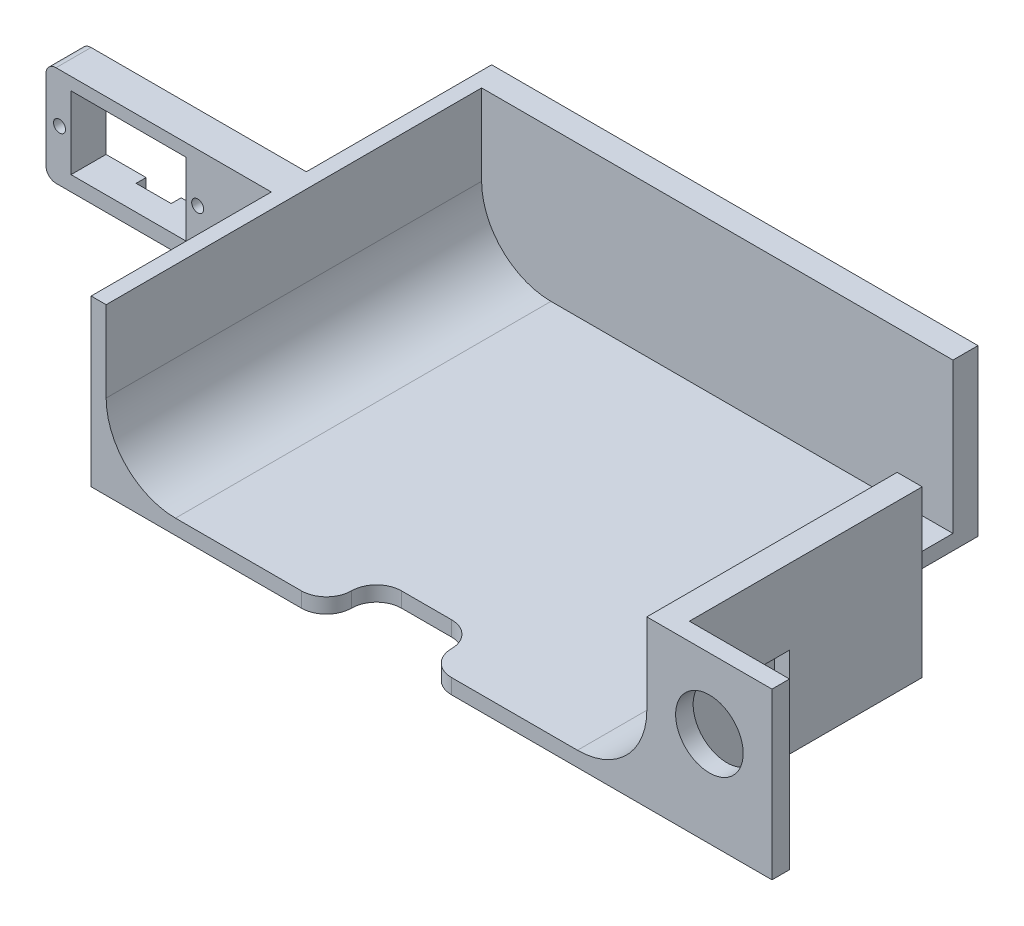
SolidWorks part; units mm, degrees
ref_plane "Plan de face" through (0, 0, 0) normal (0, 0, 1) x (1, 0, 0)
ref_plane "Plan de dessus" through (0, 0, 0) normal (0, 1, 0) x (1, 0, 0)
ref_plane "Plan de droite" through (0, 0, 0) normal (1, 0, 0) x (0, 0, -1)
sketch "Esquisse1" plane through (0, 0, 0) normal (0, 1, 0) x (1, 0, 0)
  line L1 (0, 0) -> (138, 0)
  line L2 (0, 0) -> (0, 75)
  line L3 (0, 75) -> (138, 75)
  line L4 (138, 0) -> (138, 75)
  dimension "D1" = 138
  dimension "D2" = 75
extrude "Boss.-Extru.1" add sketch "Esquisse1" along normal blind 3
sketch "Esquisse2" plane through (0, 3, 0) normal (0, 1, 0) x (1, 0, 0)
  line L0 (0, 0) -> (138, 0) construction
  line L1 (0, 75) -> (5, 75)
  line L2 (0, 75) -> (0, 0)
  line L3 (0, 0) -> (5, 0)
  line L4 (5, 75) -> (5, 0)
  line L6 (138, 75) -> (113, 75)
  line L7 (138, 75) -> (138, 0)
  line L8 (138, 0) -> (113, 0)
  line L9 (113, 75) -> (113, 0)
  dimension "D1" = 25
  dimension "D2" = 5
extrude "Boss.-Extru.2" add sketch "Esquisse2" along normal blind 30
fillet "Congé1" radius 13.85 2 edges at (113, 3, -37.5) (5, 3, -37.5)
sketch "Esquisse3" plane through (0, 0, -75) normal (0, 0, -1) x (-1, 0, 0)
  line L1 (-138, 0) -> (0, 0)
  line L2 (-138, 0) -> (-138, 33)
  line L3 (-138, 33) -> (0, 33)
  line L4 (0, 0) -> (0, 33)
extrude "Boss.-Extru.3" add sketch "Esquisse3" along normal blind 5
sketch "Esquisse4" plane through (0, 0, 0) normal (-1, 0, 0) x (0, 0, 1)
  line L1 (0, 33) -> (-25, 33)
  line L2 (0, 33) -> (0, 13)
  line L3 (0, 13) -> (-25, 13)
  line L4 (-25, 33) -> (-25, 13)
  dimension "D1" = 25
  dimension "D2" = 20
extrude "Enlèv. mat.-Extru.1" [suppressed] cut sketch "Esquisse4" against normal blind 6
sketch "Esquisse5" plane through (0, 33, 0) normal (0, 1, 0) x (1, 0, 0)
  line L0 (113, 75) -> (113, 0) construction
  line L1 (138, 80) -> (118, 80)
  line L2 (138, 80) -> (138, 3.5)
  line L3 (138, 3.5) -> (118, 3.5)
  line L4 (118, 80) -> (118, 3.5)
  line L5 (113, 0) -> (138, 0) construction
  dimension "D1" = 5
  dimension "D2" = 3.5
extrude "Enlèv. mat.-Extru.2" cut sketch "Esquisse5" against normal blind 30
sketch "Esquisse6" plane through (0, 0, 0) normal (0, 0, 1) x (1, 0, 0)
  line L0 (113, 33) -> (138, 33) construction
  line L3 (138, 33) -> (138, 0) construction
  circle A0 centre (125.5, 19) radius 6.25
  dimension "D3" = 12.5
  dimension "D1" = 14
  dimension "D2" = 12.5
extrude "Enlèv. mat.-Extru.3" cut sketch "Esquisse6" against normal up to surface (3.5 mm away) up to face at (128, 18, -3.5)
sketch "Esquisse7" plane through (0, 0, -80) normal (0, 0, -1) x (-1, 0, 0)
  line L1 (-138, 0) -> (-118, 0)
  line L2 (-138, 0) -> (-138, 3)
  line L3 (-138, 3) -> (-118, 3)
  line L4 (-118, 0) -> (-118, 3)
extrude "Enlèv. mat.-Extru.4" cut sketch "Esquisse7" against normal blind 30
sketch "Esquisse8" plane through (0, 33, 0) normal (0, 1, 0) x (1, 0, 0)
  line L0 (99.15, 0) -> (99.15, 75) construction
  line L1 (118, 80) -> (99.15, 80)
  line L2 (118, 80) -> (118, 50)
  line L3 (118, 50) -> (99.15, 50)
  line L4 (99.15, 80) -> (99.15, 50)
  dimension "D1" = 30
extrude "Enlèv. mat.-Extru.5" cut sketch "Esquisse8" against normal up to surface (33 mm away) up to face at (85.3333, 0, -43.3333)
sketch "Esquisse10" plane through (118, 0, 0) normal (1, 0, 0) x (0, 0, -1)
  line L0 (50, 3) -> (3.5, 3) construction
  line L1 (15.5, 3) -> (23.5, 3)
  line L2 (15.5, 3) -> (15.5, 18)
  line L3 (15.5, 18) -> (23.5, 18)
  line L4 (23.5, 3) -> (23.5, 18)
  dimension "D1" = 12
  dimension "D2" = 8
  dimension "D3" = 15
extrude "Enlèv. mat.-Extru.6" cut sketch "Esquisse10" against normal offset from surface (3 mm away) 2 up to face at (113, 24.925, -25)
sketch "Esquisse11" plane through (0, 3, 0) normal (0, 1, 0) x (1, 0, 0)
  line L1 (115, 23.5) -> (118, 23.5)
  line L2 (115, 23.5) -> (115, 15.5)
  line L3 (115, 15.5) -> (131, 15.5)
  line L8 (138, 3.5) -> (131, 3.5)
  line L9 (131, 15.5) -> (131, 3.5)
  line L10 (138, 50) -> (138, 3.5)
  line L11 (118, 50) -> (138, 50)
  line L12 (118, 50) -> (118, 23.5)
  dimension "D1" = 12
  dimension "D2" = 7
  dimension "D3" = 20
extrude "Enlèv. mat.-Extru.7" cut sketch "Esquisse11" against normal up to surface (3 mm away) up to face at (79.05, 0, -43.3333)
sketch "Esquisse12" plane through (0, 0, 0) normal (-1, 0, 0) x (0, 0, 1)
  line L1 (-80, 33) -> (0, 33)
  line L2 (-80, 33) -> (-80, 0)
  line L3 (-80, 0) -> (0, 0)
  line L4 (0, 33) -> (0, 0)
extrude "Enlèv. mat.-Extru.8" cut sketch "Esquisse12" against normal blind 2
sketch "Esquisse13" plane through (0, 0, 0) normal (0, 0, 1) x (1, 0, 0)
  line L0 (37, 0) -> (44.5969, -20)
  line L1 (2, 0) -> (138, 0) construction
  line L2 (44.5969, -20) -> (71.5969, -20)
  line L3 (71.5969, -20) -> (78, 0)
  line L4 (78, 0) -> (37, 0)
  line L7 (113, 33) -> (113, 16.85) construction
  dimension "D1" = 35
  dimension "D2" = 27
  dimension "D3" = 35
  dimension "D4" = 20
  dimension "D5" = 21
extrude "Boss.-Extru.4" [suppressed] add sketch "Esquisse13" against normal blind 7
sketch "Esquisse14" [suppressed] plane through (0, 0, 0) normal (0, 0, 1) x (1, 0, 0)
  line L0 (44.5969, -20) -> (71.5969, -20) construction
  line L1 (46.5, -2.5) -> (69.5, -2.5)
  line L2 (46.5, -2.5) -> (46.5, -17)
  line L3 (46.5, -17) -> (69.5, -17)
  line L4 (69.5, -2.5) -> (69.5, -17)
  dimension "D1" = 23
  dimension "D2" = 9.5
  dimension "D3" = 3
  dimension "D4" = 14.5
extrude "Enlèv. mat.-Extru.9" [suppressed] cut sketch "Esquisse14" against normal up to surface (7 mm away) up to face at (131.75, 19, 0)
fillet "Congé2" [suppressed] radius 10
sketch "Esquisse15" plane through (2, 0, 0) normal (-1, 0, 0) x (0, 0, 1)
  line L0 (0, 33) -> (-80, 33) construction
  line L1 (-42.9875, 33) -> (-35.9875, 33)
  line L2 (-42.9875, 33) -> (-42.9875, 13)
  line L3 (-42.9875, 13) -> (-35.9875, 13)
  line L4 (-35.9875, 33) -> (-35.9875, 13)
  dimension "D1" = 20
  dimension "D2" = 7
extrude "Boss.-Extru.5" add sketch "Esquisse15" along normal blind 45
sketch "Esquisse16" plane through (0, 0, -35.9875) normal (0, 0, 1) x (1, 0, 0)
  line L0 (-20.5, 33) -> (-20.5, 13) construction
  line L1 (-43, 33) -> (2, 33) construction
  line L2 (-43, 13) -> (2, 13) construction
  line L3 (-43, 23) -> (2, 23) construction
  line L4 (-43, 13) -> (-43, 33) construction
  line L5 (2, 13) -> (2, 33) construction
  line L7 (-38, 30.5) -> (-15, 30.5)
  line L8 (-38, 30.5) -> (-38, 16)
  line L9 (-38, 16) -> (-15, 16)
  line L10 (-15, 30.5) -> (-15, 16)
  dimension "D1" = 23
  dimension "D2" = 14.5
  dimension "D3" = 2.5
  dimension "D4" = 5
extrude "Enlèv. mat.-Extru.10" cut sketch "Esquisse16" against normal up to surface (7 mm away) up to face at (-20.5, 23, -42.9875)
fillet "Congé3" radius 20 1 edges at (2, 13, -39.4875)
fillet "Congé4" radius 2 2 edges at (-43, 33, -39.4875) (-43, 13, -39.4875)
sketch "Esquisse18" plane through (0, 0, -42.9875) normal (0, 0, -1) x (-1, 0, 0)
  line L0 (15, 16) -> (38, 16) construction
  line L1 (23, 16) -> (30, 16)
  line L2 (23, 16) -> (23, 13)
  line L3 (23, 13) -> (30, 13)
  line L4 (30, 16) -> (30, 13)
  line L6 (41, 13) -> (16.735, 13) construction
  dimension "D1" = 8
  dimension "D2" = 8
extrude "Enlèv. mat.-Extru.11" cut sketch "Esquisse18" against normal blind 2
sketch "Esquisse20" plane through (0, 0, -42.9875) normal (0, 0, -1) x (-1, 0, 0)
  line L0 (38, 30.5) -> (15, 30.5) construction
  line L1 (10.4, 25.9) -> (15, 25.9)
  line L2 (10.4, 25.9) -> (10.4, 20.6)
  line L3 (10.4, 20.6) -> (15, 20.6)
  line L4 (15, 25.9) -> (15, 20.6)
  line L5 (38, 25.9) -> (42.6, 25.9)
  line L6 (38, 25.9) -> (38, 20.6)
  line L7 (38, 20.6) -> (42.6, 20.6)
  line L8 (42.6, 25.9) -> (42.6, 20.6)
  line L9 (15, 16) -> (23, 16) construction
  line L10 (15, 30.5) -> (15, 16) construction
  line L11 (38, 16) -> (38, 30.5) construction
  line L12 (30, 16) -> (38, 16) construction
  dimension "D1" = 4.6
  dimension "D2" = 4.6
  dimension "D3" = 4.6
  dimension "D4" = 4.6
  dimension "D5" = 4.6
  dimension "D6" = 4.6
sketch "Esquisse21" plane through (0, 0, -42.9875) normal (0, 0, -1) x (-1, 0, 0)
  line L0 (15, 25.9) -> (15, 20.6) construction
  line L1 (10.4, 25.9) -> (10.4, 20.6) construction
  line L2 (10.4, 23.25) -> (15, 23.25) construction
  line L3 (15, 23.25) -> (42.6, 23.25) construction
  line L4 (42.6, 25.9) -> (42.6, 20.6) construction
  circle A0 centre (12.7, 23.25) radius 1
  circle A1 centre (40.3, 23.25) radius 1
  dimension "D1" = 2
  dimension "D3" = 2
  dimension "D2" = 2.3
extrude "Enlèv. mat.-Extru.12" cut sketch "Esquisse21" against normal up to surface (7 mm away) up to face at (-26.5, 23.25, -35.9875)
hole_wizard "Dégagement M21" positions "Esquisse22" profile "Esquisse23" hole size "M2" standard "ISO"
sketch "Esquisse22" plane through (0, 0, -42.9875) normal (0, 0, -1) x (-1, 0, 0)
  point P0 (40.3, 23.25)
  point P3 (12.7, 23.25)
sketch "Esquisse23" plane through (-40.3, 23.25, -42.9875) normal (1, 0, 0) x (0, 1, 0)
  line L0 (0, 0) -> (0, 10.721)
  line L1 (0, 10.721) -> (1.2, 10)
  line L2 (1.2, 10) -> (1.2, 0)
  line L5 (1.2, 0) -> (0, 0)
  line L10 (0, 10.721) -> (-1.2, 10) construction
  line L11 (0, -6.35) -> (0, 107.95) construction
  dimension "Diamètre du perçage" = 2.4
  dimension "Profondeur du perçage" = 10
  dimension "Angle de pointe" = 118
hole_wizard "Dégagement M121" positions "Esquisse24" profile "Esquisse25" hole size "M12" standard "ISO"
sketch "Esquisse24" plane through (0, 0, 0) normal (0, 0, 1) x (1, 0, 0)
  point P0 (125.5, 19)
sketch "Esquisse25" plane through (125.5, 19, 0) normal (1, 0, 0) x (0, -1, 0)
  line L0 (0, 0) -> (0, 14.0558)
  line L1 (0, 14.0558) -> (6.75, 10)
  line L2 (6.75, 10) -> (6.75, 0)
  line L5 (6.75, 0) -> (0, 0)
  line L10 (0, 14.0558) -> (-6.75, 10) construction
  line L11 (0, -6.35) -> (0, 107.95) construction
  dimension "Diamètre du perçage" = 13.5
  dimension "Profondeur du perçage" = 10
  dimension "Angle de pointe" = 118
sketch "Esquisse26" plane through (0, 0, 0) normal (0, 0, 1) x (1, 0, 0)
  line L0 (5, 33) -> (113, 33) construction
  line L1 (59, 33) -> (59, 0) construction
  line L2 (2, 0) -> (138, 0) construction
  line L3 (59, 3) -> (49, 3)
  line L4 (18.85, 3) -> (99.15, 3) construction
  line L5 (49, 3) -> (49, 0)
  line L6 (49, 0) -> (69, 0)
  line L7 (69, 0) -> (69, 3)
  line L8 (99.15, 3) -> (18.85, 3) construction
  line L9 (69, 3) -> (59, 3)
  dimension "D1" = 10
  dimension "D2" = 10
extrude "Enlèv. mat.-Extru.13" cut sketch "Esquisse26" against normal blind 10
fillet "Congé5" radius 5 4 edges at (69, 1.5, 0) (49, 1.5, 0) (49, 1.5, -10) (69, 1.5, -10)
sketch "Esquisse27" plane through (0, 0, 0) normal (0, -1, 0) x (1, 0, 0)
  line L0 (2, -80) -> (2, -42.9875) construction
  line L1 (2, -35.9875) -> (-8, -35.9875)
  line L2 (2, -35.9875) -> (2, -25.9875)
  line L3 (2, -25.9875) -> (-8, -25.9875)
  line L4 (-8, -35.9875) -> (-8, -25.9875)
  line L5 (2, -60) -> (-8, -60)
  line L6 (2, -60) -> (2, -70)
  line L7 (2, -70) -> (-8, -70)
  line L8 (-8, -60) -> (-8, -70)
  line L9 (99.15, -80) -> (2, -80) construction
  line L11 (12, -80) -> (22, -80)
  line L12 (12, -80) -> (12, -90)
  line L13 (12, -90) -> (22, -90)
  line L14 (22, -80) -> (22, -90)
  dimension "D1" = 10
  dimension "D2" = 10
  dimension "D3" = 10
  dimension "D4" = 10
  dimension "D5" = 10
  dimension "D6" = 10
  dimension "D7" = 10
  dimension "D8" = 10
extrude "Boss.-Extru.6" add sketch "Esquisse27" against normal blind 7
sketch "Esquisse28" plane through (0, 0, 0) normal (0, -1, 0) x (1, 0, 0)
  line L0 (118, -50) -> (99.15, -68.85)
  line L1 (99.15, -80) -> (99.15, -50) construction
  line L2 (99.15, -68.85) -> (99.15, -50)
  line L3 (99.15, -50) -> (118, -50)
  dimension "D1" = 18.85
extrude "Boss.-Extru.7" add sketch "Esquisse28" against normal blind 3
sketch "Esquisse31" plane through (0, 0, 0) normal (0, -1, 0) x (1, 0, 0)
  line L0 (2, -25.9875) -> (-8, -25.9875) construction
  line L1 (2, -25.9875) -> (2, 0) construction
  line L2 (2, -60) -> (-8, -60) construction
  line L6 (-8, -60) -> (-8, -70) construction
  line L7 (22, -90) -> (22, -80) construction
  line L8 (12, -90) -> (22, -90) construction
  line L9 (118, -50) -> (118, -23.5) construction
  circle A0 centre (-3, -30.9875) radius 1.5
  circle A1 centre (-3, -65) radius 1.5
  circle A2 centre (17, -85) radius 1.5
  circle A3 centre (104, -54.85) radius 1.5
  dimension "D3" = 3
  dimension "D6" = 3
  dimension "D8" = 3
  dimension "D11" = 3
  dimension "D1" = 5
  dimension "D2" = 5
  dimension "D4" = 5
  dimension "D5" = 5
  dimension "D7" = 5
  dimension "D9" = 5
  dimension "D10" = 14
  dimension "D12" = 14
extrude "Enlèv. mat.-Extru.14" cut sketch "Esquisse31" against normal blind 7
hole_wizard "Fraisage pour vis à tête fraisée M31" positions "Esquisse32" profile "Esquisse33" countersink size "M3" standard "ISO"
sketch "Esquisse32" plane through (0, 3, 0) normal (0, 1, 0) x (1, 0, 0)
  point P0 (104, 54.85)
sketch "Esquisse33" plane through (104, 3, -54.85) normal (1, 0, 0) x (0, 0, 1)
  line L0 (0, 0) -> (0, 11.0215)
  line L1 (0, 11.0215) -> (1.7, 10)
  line L2 (1.7, 10) -> (1.7, 1.45)
  line L3 (1.7, 1.45) -> (3.15, 0)
  line L5 (3.15, 0) -> (0, 0)
  line L6 (-1.7, 1.45) -> (-3.15, 0) construction
  line L10 (0, 11.0215) -> (-1.7, 10) construction
  line L11 (0, -6.35) -> (0, 107.95) construction
  dimension "Diamètre du perçage" = 3.4
  dimension "Profondeur du perçage" = 10
  dimension "Diamètre du fraisage entrant" = 6.3
  dimension "Angle du fraisage entrant" = 90
  dimension "Angle de pointe" = 118
hole_wizard "Fraisage pour vis à tête fraisée M32" positions "Esquisse34" profile "Esquisse35" countersink size "M3" standard "ISO"
sketch "Esquisse34" plane through (0, 7, 0) normal (0, 1, 0) x (1, 0, 0)
  point P0 (-3, 30.9875)
  point P3 (-3, 65)
  point P6 (17, 85)
sketch "Esquisse35" plane through (-3, 7, -30.9875) normal (1, 0, 0) x (0, 0, 1)
  line L0 (0, 0) -> (0, 11.0215)
  line L1 (0, 11.0215) -> (1.7, 10)
  line L2 (1.7, 10) -> (1.7, 1.45)
  line L3 (1.7, 1.45) -> (3.15, 0)
  line L5 (3.15, 0) -> (0, 0)
  line L6 (-1.7, 1.45) -> (-3.15, 0) construction
  line L10 (0, 11.0215) -> (-1.7, 10) construction
  line L11 (0, -6.35) -> (0, 107.95) construction
  dimension "Diamètre du perçage" = 3.4
  dimension "Profondeur du perçage" = 10
  dimension "Diamètre du fraisage entrant" = 6.3
  dimension "Angle du fraisage entrant" = 90
  dimension "Angle de pointe" = 118
sketch "Esquisse36" plane through (0, 3, 0) normal (0, 1, 0) x (1, 0, 0)
  line L1 (131, 15.5) -> (118, 15.5)
  line L2 (131, 15.5) -> (131, 3.5)
  line L3 (131, 3.5) -> (118, 3.5)
  line L4 (118, 15.5) -> (118, 3.5)
extrude "Enlèv. mat.-Extru.15" cut sketch "Esquisse36" against normal up to surface (3 mm away) up to face at (-3, 0, -32.6875)
